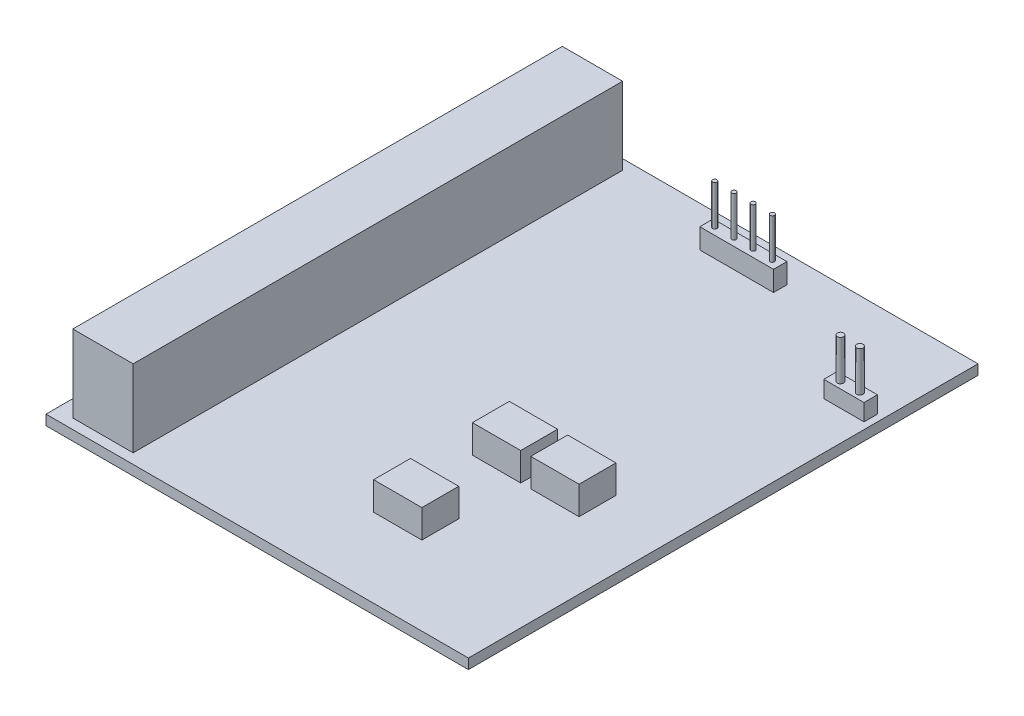
SolidWorks part; units mm, degrees
ref_plane "Front Plane" through (0, 0, 0) normal (0, 0, 1) x (1, 0, 0)
ref_plane "Top Plane" through (0, 0, 0) normal (0, 1, 0) x (1, 0, 0)
ref_plane "Right Plane" through (0, 0, 0) normal (1, 0, 0) x (0, 0, -1)
sketch "Sketch1" plane through (0, 0, 0) normal (0, 1, 0) x (1, 0, 0)
  line L1 (0, 0) -> (63, 0)
  line L2 (0, 0) -> (0, 76)
  line L3 (0, 76) -> (63, 76)
  line L4 (63, 0) -> (63, 76)
  dimension "D1" = 63
  dimension "D2" = 76
extrude "Boss-Extrude1" add sketch "Sketch1" along normal blind 1.5
sketch "Sketch2" plane through (0, 1.5, 0) normal (0, 1, 0) x (1, 0, 0)
  line L0 (63, 76) -> (0, 76) construction
  line L1 (2.5, 74.5) -> (11.5, 74.5)
  line L2 (2.5, 74.5) -> (2.5, 1.5)
  line L3 (2.5, 1.5) -> (11.5, 1.5)
  line L4 (11.5, 74.5) -> (11.5, 1.5)
  line L5 (0, 76) -> (0, 0) construction
  dimension "D1" = 73
  dimension "D2" = 1.5
  dimension "D3" = 2.5
  dimension "D4" = 9
extrude "Boss-Extrude2" add sketch "Sketch2" along normal blind 11.5
sketch "Sketch3" plane through (0, 0, 0) normal (0, -1, 0) x (1, 0, 0)
  line L0 (0, -76) -> (0, 0) construction
  line L1 (9, -15) -> (16, -15)
  line L2 (9, -15) -> (9, -23)
  line L3 (9, -23) -> (16, -23)
  line L4 (16, -15) -> (16, -23)
  line L5 (9, -34) -> (16, -34)
  line L6 (9, -34) -> (9, -42)
  line L7 (9, -42) -> (16, -42)
  line L8 (16, -34) -> (16, -42)
  line L9 (9, -56) -> (16, -56)
  line L10 (9, -56) -> (9, -64)
  line L11 (9, -64) -> (16, -64)
  line L12 (16, -56) -> (16, -64)
  line L13 (63, -76) -> (0, -76) construction
  dimension "D1" = 8
  dimension "D2" = 8
  dimension "D3" = 8
  dimension "D4" = 7
  dimension "D5" = 7
  dimension "D6" = 7
  dimension "D7" = 9
  dimension "D8" = 9
  dimension "D9" = 9
  dimension "D10" = 12
  dimension "D11" = 34
  dimension "D12" = 53
extrude "Boss-Extrude3" add sketch "Sketch3" along normal blind 3.5
sketch "Sketch4" plane through (0, 1.5, 0) normal (0, 1, 0) x (1, 0, 0)
  line L1 (27.5447, 71.9574) -> (38.5447, 71.9574)
  line L2 (27.5447, 71.9574) -> (27.5447, 69.9574)
  line L3 (27.5447, 69.9574) -> (38.5447, 69.9574)
  line L4 (38.5447, 71.9574) -> (38.5447, 69.9574)
  dimension "D1" = 11
  dimension "D2" = 2
extrude "Boss-Extrude4" add sketch "Sketch4" along normal blind 3
sketch "Sketch5" plane through (0, 4.5, 0) normal (0, 1, 0) x (1, 0, 0)
  line L0 (27.5447, 71.9574) -> (27.5447, 69.9574) construction
  circle A0 centre (28.7447, 71.0035) radius 0.325
  circle A1 centre (31.6047, 71.0035) radius 0.325
  circle A2 centre (34.4647, 71.0035) radius 0.325
  circle A3 centre (37.3247, 71.0035) radius 0.325
  dimension "D1" = 0.65
  dimension "D2" = 1.2
  dimension "D3" = 4
extrude "Boss-Extrude5" add sketch "Sketch5" along normal blind 6
sketch "Sketch6" plane through (0, 1.5, 0) normal (0, 1, 0) x (1, 0, 0)
  line L0 (63, 0) -> (63, 76) construction
  line L1 (56, 62) -> (62, 62)
  line L2 (56, 62) -> (56, 60)
  line L3 (56, 60) -> (62, 60)
  line L4 (62, 62) -> (62, 60)
  line L5 (63, 76) -> (0, 76) construction
  dimension "D1" = 6
  dimension "D2" = 2
  dimension "D3" = 1
  dimension "D4" = 14
extrude "Boss-Extrude6" add sketch "Sketch6" along normal blind 2.5
sketch "Sketch7" plane through (0, 4, 0) normal (0, 1, 0) x (1, 0, 0)
  line L0 (56, 62) -> (56, 60) construction
  circle A0 centre (57.5, 60.989) radius 0.4731
  circle A1 centre (60.4, 60.989) radius 0.4731
  dimension "D1" = 1.5
  dimension "D2" = 2
extrude "Boss-Extrude7" add sketch "Sketch7" along normal blind 6
sketch "Sketch8" plane through (0, 1.5, 0) normal (0, 1, 0) x (1, 0, 0)
  line L0 (63, 0) -> (63, 76) construction
  line L1 (37.1, 32) -> (44.3, 32)
  line L2 (37.1, 32) -> (37.1, 26.5)
  line L3 (37.1, 26.5) -> (44.3, 26.5)
  line L4 (44.3, 32) -> (44.3, 26.5)
  line L5 (45.8, 32) -> (53, 32)
  line L6 (45.8, 32) -> (45.8, 26.5)
  line L7 (45.8, 26.5) -> (53, 26.5)
  line L8 (53, 32) -> (53, 26.5)
  line L9 (37.1, 17.26) -> (44.3, 17.26)
  line L10 (37.1, 17.26) -> (37.1, 11.76)
  line L11 (37.1, 11.76) -> (44.3, 11.76)
  line L12 (44.3, 17.26) -> (44.3, 11.76)
  line L13 (0, 0) -> (63, 0) construction
  dimension "D1" = 7.2
  dimension "D2" = 7.2
  dimension "D3" = 7.2
  dimension "D4" = 5.5
  dimension "D5" = 5.5
  dimension "D6" = 5.5
  dimension "D7" = 10
  dimension "D8" = 18.7
  dimension "D9" = 18.7
  dimension "D10" = 11.76
  dimension "D11" = 26.5
  dimension "D12" = 26.5
extrude "Boss-Extrude8" add sketch "Sketch8" along normal blind 4.2
